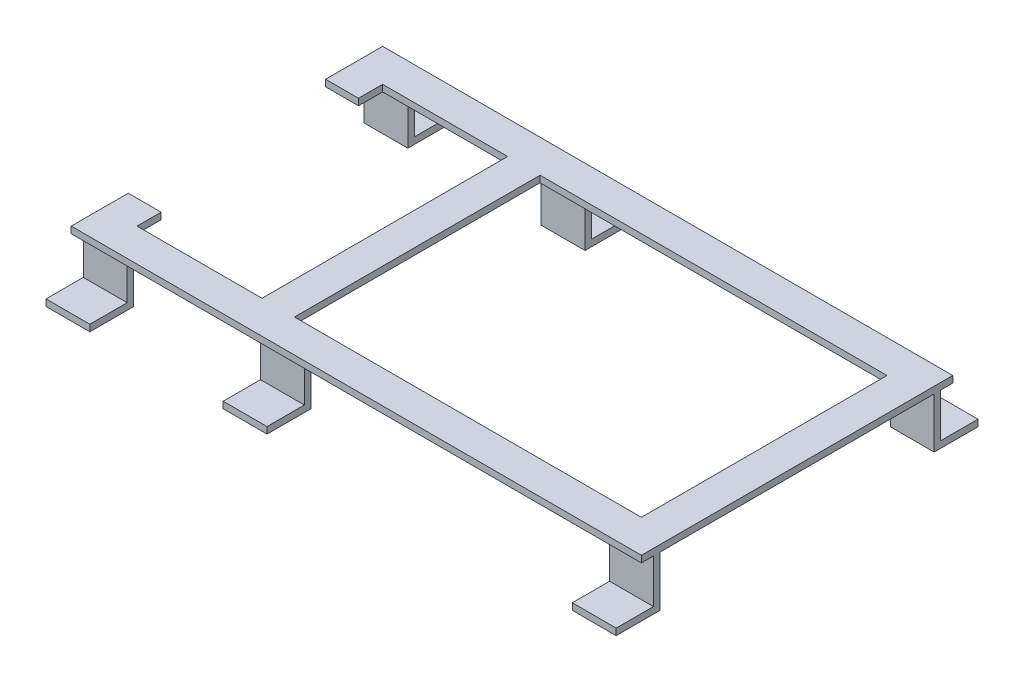
SolidWorks part; units mm, degrees
ref_plane "Alzado" through (0, 0, 0) normal (0, 0, 1) x (1, 0, 0)
ref_plane "Planta" through (0, 0, 0) normal (0, 1, 0) x (1, 0, 0)
ref_plane "Vista lateral" through (0, 0, 0) normal (1, 0, 0) x (0, 0, -1)
sketch "Croquis1" plane through (0, 0, 0) normal (0, 1, 0) x (1, 0, 0)
  line L0 (115, 56) -> (-115, 56)
  line L1 (130, -71) -> (-130, -71)
  line L2 (130, -71) -> (130, 71)
  line L3 (130, 71) -> (-130, 71)
  line L4 (-130, -71) -> (-130, 71)
  line L5 (130, -71) -> (-130, 71) construction
  line L6 (130, 71) -> (-130, -71) construction
  line L7 (-115, -56) -> (-115, 56)
  line L8 (115, -56) -> (-115, -56)
  line L9 (115, -56) -> (115, 56)
  point P0 (0, 0)
  dimension "D1" = 142
  dimension "D2" = 260
  dimension "D3" = 15
extrude "Saliente-Extruir1" add sketch "Croquis1" along normal blind 3
ref_plane "Plano1" through (-130, 0, 0) normal (1, 0, 0) x (0, 0, -1)
sketch "Croquis2" plane through (-130, 0, 0) normal (-1, 0, 0) x (0, 0, 1)
  line L0 (65.5, 0) -> (65.5, -20)
  line L6 (62.5, 0) -> (65.5, 0)
  line L8 (82.5, -23) -> (82.5, -20)
  line L9 (82.5, -20) -> (65.5, -20)
  line L20 (62.5, 0) -> (62.5, -23)
  line L21 (62.5, -23) -> (82.5, -23)
  line L22 (71, 3) -> (71, 0) construction
  line L23 (-71, 0) -> (71, 0) construction
  dimension "D1" = 23
  dimension "D2" = 3
  dimension "D3" = 5.5
  dimension "D4" = 20
  dimension "D5" = 3
extrude "Saliente-Extruir2" add sketch "Croquis2" against normal blind 20
mirror "Simetría1" about plane through (0, 0, 0) normal (1, 0, 0) of "Saliente-Extruir2"
mirror "Simetría2" about plane through (0, 0, 0) normal (0, 0, 1) of "Simetría1"
sketch "Croquis3" plane through (0, 3, 0) normal (0, 1, 0) x (1, 0, 0)
  line L1 (-120, 32.5) -> (-60, 32.5)
  line L2 (-120, 32.5) -> (-120, -32.5)
  line L3 (-120, -32.5) -> (-60, -32.5)
  line L4 (-60, 32.5) -> (-60, -32.5)
  point P4 (-60, 0)
  dimension "D1" = 65
  dimension "D2" = 60
  dimension "D3" = 60
extrude "Cortar-Extruir1" [suppressed] cut sketch "Croquis3" against normal through all
mirror "Simetría3" [suppressed] about plane through (0, 0, 0) normal (1, 0, 0)
ref_plane "Plano2" through (-39.2, 0, 0) normal (1, 0, 0) x (0, 0, -1)
sketch "Croquis4" plane through (-39.2, 0, 0) normal (1, 0, 0) x (0, 0, -1)
  line L12 (-71, 0) -> (-65.5, 0)
  line L13 (-65.5, 0) -> (-65.5, -20)
  line L14 (-65.5, -20) -> (-82.5, -20)
  line L15 (-82.5, -20) -> (-82.5, -23)
  line L16 (-82.5, -23) -> (-62.5, -23)
  line L17 (-82.5, -23) -> (-62.5, -23)
  line L19 (-65.5, 0) -> (-65.5, -20)
  line L20 (-65.5, -20) -> (-82.5, -20)
  line L21 (-82.5, -20) -> (-82.5, -23)
  line L38 (-62.5, -23) -> (-62.5, 0)
  line L40 (-62.5, -23) -> (-62.5, 0)
  line L42 (62.5, 0) -> (62.5, -23)
  line L44 (62.5, 0) -> (62.5, -23)
  line L47 (62.5, -23) -> (82.5, -23)
  line L49 (82.5, -23) -> (82.5, -20)
  line L50 (62.5, -23) -> (82.5, -23)
  line L54 (82.5, -23) -> (82.5, -20)
  line L56 (82.5, -20) -> (65.5, -20)
  line L58 (82.5, -20) -> (65.5, -20)
  line L60 (71, 0) -> (71, 3)
  line L61 (71, 0) -> (71, 3)
  line L62 (71, 3) -> (-71, 3)
  line L63 (71, 3) -> (-71, 3)
  line L70 (-71, 0) -> (-65.5, 0)
  line L71 (-62.5, 0) -> (62.5, 0)
  line L72 (-62.5, 0) -> (62.5, 0)
  line L73 (65.5, -20) -> (65.5, 0)
  line L74 (65.5, -20) -> (65.5, 0)
  line L75 (65.5, 0) -> (71, 0)
  line L76 (65.5, 0) -> (71, 0)
  line L77 (-71, 3) -> (-71, 0)
  line L78 (-71, 3) -> (-71, 0)
  dimension "D1" = 0
extrude "Saliente-Extruir3" add sketch "Croquis4" along normal mid plane 20
mirror "Simetría4" about plane through (0, 0, 0) normal (0, 0, 1) of "Saliente-Extruir3"
sketch "Croquis5" plane through (0, 3, 0) normal (0, 1, 0) x (1, 0, 0)
  line L1 (-105.499, -45) -> (-143.7054, -45)
  line L2 (-105.499, -45) -> (-105.499, 45)
  line L3 (-105.499, 45) -> (-143.7054, 45)
  line L4 (-143.7054, -45) -> (-143.7054, 45)
  line L5 (-105.499, -45) -> (-143.7054, 45) construction
  line L6 (-105.499, 45) -> (-143.7054, -45) construction
  point P0 (-124.6022, 0)
  point P5 (0, 0)
  dimension "D1" = 90
extrude "Cortar-Extruir2" cut sketch "Croquis5" against normal through all
sketch "Croquis6" plane through (0, 3, 0) normal (0, 1, 0) x (1, 0, 0)
  line L0 (-53, 56) -> (-53, -56) construction
  line L1 (115, 56) -> (-29.2, 56) construction
  line L2 (-29.2, -56) -> (115, -56) construction
  line L4 (-130, -45) -> (-130, -71) construction
  line L6 (-58, 56) -> (-48, 56)
  line L7 (-58, 56) -> (-58, -56)
  line L8 (-58, -56) -> (-48, -56)
  line L9 (-48, 56) -> (-48, -56)
  point P12 (-53, 56)
  point P13 (-53, -56)
  dimension "D1" = 77
  dimension "D2" = 10
extrude "Saliente-Extruir4" add sketch "Croquis6" against normal up to surface (3 mm away) up to face at (-39.2, 0, -64)
sketch "Croquis7" plane through (0, 3, 0) normal (0, 1, 0) x (1, 0, 0)
  line L1 (-43.2, 56) -> (-29.2, 56)
  line L2 (-43.2, 56) -> (-43.2, -56)
  line L3 (-43.2, -56) -> (-29.2, -56)
  line L4 (-29.2, 56) -> (-29.2, -56)
extrude "Cortar-Extruir3" cut sketch "Croquis7" against normal through all
